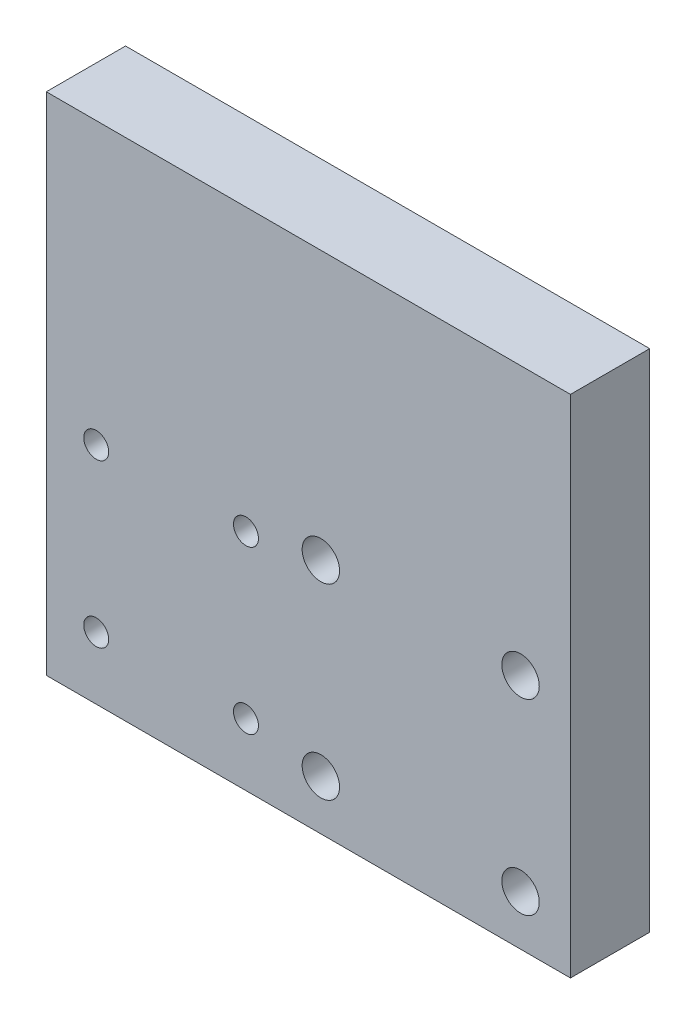
SolidWorks part; units mm, degrees
ref_plane "Front Plane" through (0, 0, 0) normal (0, 0, 1) x (1, 0, 0)
ref_plane "Top Plane" through (0, 0, 0) normal (0, 1, 0) x (1, 0, 0)
ref_plane "Right Plane" through (0, 0, 0) normal (1, 0, 0) x (0, 0, -1)
sketch "Sketch1" plane through (0, 0, 0) normal (0, 0, 1) x (1, 0, 0)
  line L0 (-8, 7.5) -> (8, 7.5) construction
  line L5 (-26, 6.5) -> (-14, 6.5) construction
  line L7 (-8, -7.5) -> (8, -7.5) construction
  line L8 (-8, -7.5) -> (-8, 7.5) construction
  line L9 (-8, 7.5) -> (8, 7.5) construction
  line L10 (8, -7.5) -> (8, 7.5) construction
  line L11 (-8, -7.5) -> (8, 7.5) construction
  line L12 (-8, 7.5) -> (8, -7.5) construction
  line L13 (-8, 7.5) -> (-8, -7.5) construction
  line L14 (-26, -6.5) -> (-14, -6.5) construction
  line L15 (-26, -6.5) -> (-26, 6.5) construction
  line L16 (-26, 6.5) -> (-14, 6.5) construction
  line L17 (-14, -6.5) -> (-14, 6.5) construction
  line L18 (-26, -6.5) -> (-14, 6.5) construction
  line L19 (-26, 6.5) -> (-14, -6.5) construction
  line L20 (0, 0) -> (-20, 0) construction
  line L22 (-30, -11.5) -> (12, -11.5)
  line L23 (-30, -11.5) -> (-30, 11.5)
  line L24 (-30, 11.5) -> (12, 11.5)
  line L25 (12, -11.5) -> (12, 11.5)
  line L26 (-30, -11.5) -> (12, 11.5) construction
  line L27 (-30, 11.5) -> (12, -11.5) construction
  line L28 (-11.5, -15) -> (-28.5, -15) construction
  line L29 (-11.5, -15) -> (-11.5, 15) construction
  line L30 (-11.5, 15) -> (-28.5, 15) construction
  line L31 (-28.5, -15) -> (-28.5, 15) construction
  line L32 (-11.5, -15) -> (-28.5, 15) construction
  line L33 (-11.5, 15) -> (-28.5, -15) construction
  line L34 (-59, 15) -> (41, 15)
  line L35 (-59, 15) -> (-59, 24)
  line L36 (-59, 24) -> (41, 24)
  line L37 (41, 15) -> (41, 24)
  line L38 (-59, -10) -> (41, -10) construction
  line L39 (-59, -10) -> (-59, 10) construction
  line L40 (-59, 10) -> (41, 10) construction
  line L41 (41, -10) -> (41, 10) construction
  line L42 (-59, -10) -> (41, 10) construction
  line L43 (-59, 10) -> (41, -10) construction
  line L44 (-30, -11.5) -> (12, -11.5)
  line L45 (-30, -11.5) -> (-30, 29)
  line L46 (-30, 29) -> (12, 29)
  line L47 (12, -11.5) -> (12, 29)
  circle A0 centre (-8, 7.5) radius 1.5
  circle A2 centre (8, 7.5) radius 1.5
  circle A3 centre (8, -7.5) radius 1.5
  circle A4 centre (-8, -7.5) radius 1.5
  circle A5 centre (-26, 6.5) radius 1
  circle A6 centre (-14, 6.5) radius 1
  circle A7 centre (-14, -6.5) radius 1
  circle A8 centre (-26, -6.5) radius 1
  circle A9 centre (-8, 7.5) radius 2.9 construction
  point P0 (0, 0)
  point P1 (-20, 0)
  point P4 (-9, 0)
  point P6 (0, 0)
  point P46 (-9, 15)
  point P47 (-9, 0)
  dimension "D5" = 3
  dimension "D6" = 2
  dimension "D18" = 5.8
  dimension "D1" = 15
  dimension "D2" = 16
  dimension "D3" = 13
  dimension "D4" = 12
  dimension "D9" = 16
  dimension "D10" = 15
  dimension "D13" = 12
  dimension "D14" = 20
  dimension "D15" = 23
  dimension "D16" = 4
  dimension "D17" = 4
  dimension "D19" = 17
  dimension "D20" = 30
  dimension "D21" = 9
  dimension "D22" = 100
  dimension "D23" = 20
  dimension "D24" = 100
  dimension "D25" = 15
  dimension "D26" = 40.5
  dimension "D7" = 2
  dimension "D8" = 2
  dimension "D11" = 2
  dimension "D12" = 2
extrude "Boss-Extrude1" add sketch "Sketch1" along normal blind 6.35 contours L22 L25 L24 L23 A8 A7 A6 A5 A4 A3 A2 A0 | L34 L47 L36 L45 | L24 L47 L34 L45 | L36 L47 L46 L45 region at (-9.1256, 0, 0) region at (-9, 13.25, 0) region at (-9, 19.5, 0) region at (-9, 26.5, 0)
